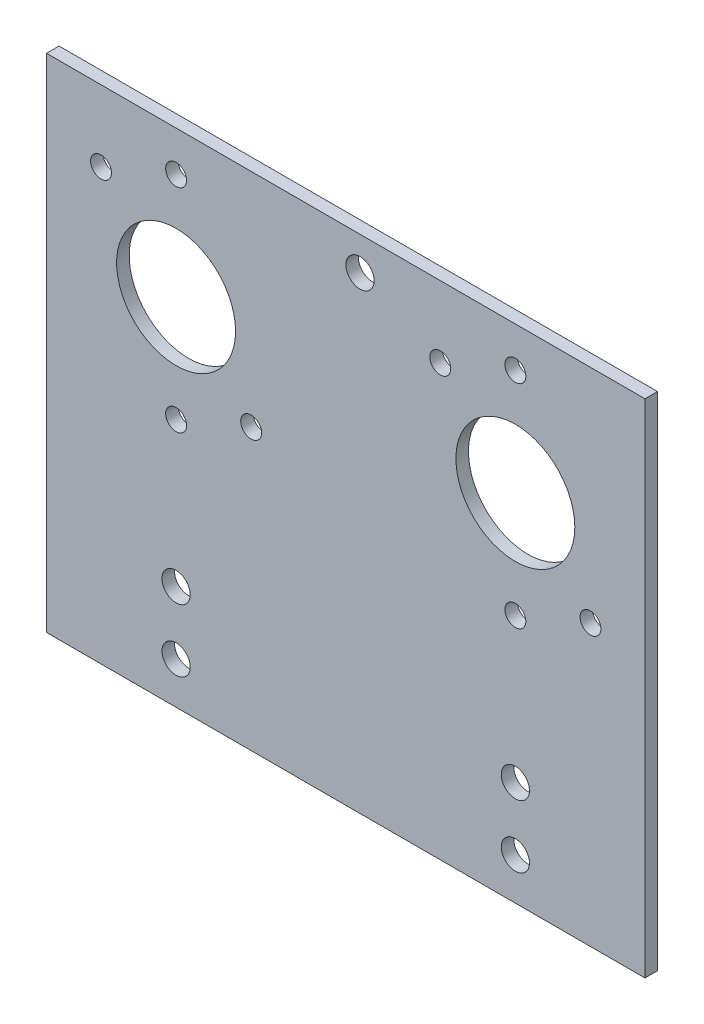
SolidWorks part; units mm, degrees
ref_plane "Front Plane" through (0, 0, 0) normal (0, 0, 1) x (1, 0, 0)
ref_plane "Top Plane" through (0, 0, 0) normal (0, 1, 0) x (1, 0, 0)
ref_plane "Right Plane" through (0, 0, 0) normal (1, 0, 0) x (0, 0, -1)
sketch "Sketch1" plane through (0, 0, 0) normal (0, 0, 1) x (1, 0, 0)
  line L1 (0, 0) -> (143.16, 0)
  line L2 (0, 0) -> (0, -120)
  line L3 (0, -120) -> (143.16, -120)
  line L4 (143.16, 0) -> (143.16, -120)
  dimension "D1" = 120
  dimension "D2" = 143.16
extrude "Boss-Extrude1" add sketch "Sketch1" along normal blind 3
sketch "Sketch2" plane through (0, 0, 3) normal (0, 0, 1) x (1, 0, 0)
  line L0 (0, 0) -> (0, -120) construction
  line L1 (143.16, -120) -> (143.16, 0) construction
  line L2 (0, -120) -> (143.16, -120) construction
  line L3 (143.16, 0) -> (0, 0) construction
  circle A0 centre (31, -35) radius 14.225
  circle A1 centre (112.16, -35) radius 14.225
  circle A2 centre (31, -110) radius 3.375
  circle A5 centre (112.16, -110) radius 3.375
  circle A7 centre (75, -8) radius 3.375
  circle A8 centre (31, -95) radius 3.375
  circle A9 centre (112.16, -95) radius 3.375
  dimension "D1" = 28.45
  dimension "D2" = 28.45
  dimension "D3" = 6.75
  dimension "D4" = 35
  dimension "D5" = 6.75
  dimension "D7" = 15
  dimension "D8" = 6.75
  dimension "D9" = 31
  dimension "D10" = 31
  dimension "D11" = 75
  dimension "D13" = 15
  dimension "D14" = 10
  dimension "D16" = 8
extrude "Cut-Extrude1" cut sketch "Sketch2" against normal through all
sketch "Sketch3" plane through (0, 0, 0) normal (0, 0, -1) x (-1, 0, 0)
  circle A0 centre (-48.9605, -52.9605) radius 2.0193 construction
  circle A1 centre (-31, -9.6) radius 2.0193 construction
  circle A2 centre (-13.0395, -17.0395) radius 2.0193 construction
  circle A3 centre (-48.9605, -52.9605) radius 2.0193
  circle A4 centre (-31, -9.6) radius 2.0193
  circle A5 centre (-13.0395, -17.0395) radius 2.0193
  circle A6 centre (-31, -60.4) radius 2.0193 construction
  circle A7 centre (-31, -60.4) radius 2.0193
  circle A8 centre (-94.1995, -17.0395) radius 2.0193 construction
  circle A9 centre (-112.16, -9.6) radius 2.0193 construction
  circle A10 centre (-94.1995, -17.0395) radius 2.0193
  circle A11 centre (-112.16, -9.6) radius 2.0193
  circle A12 centre (-112.16, -60.4) radius 2.0193 construction
  circle A13 centre (-130.1205, -52.9605) radius 2.0193 construction
  circle A14 centre (-112.16, -60.4) radius 2.0193
  circle A15 centre (-130.1205, -52.9605) radius 2.0193
  point P25 (-31, -60.4)
  point P26 (-48.9605, -52.9605)
  point P27 (-31, -9.6)
  point P28 (-13.0395, -17.0395)
  point P29 (-112.16, -60.4)
  point P30 (-130.1205, -52.9605)
  point P31 (-112.16, -9.6)
  point P32 (-94.1995, -17.0395)
extrude "Cut-Extrude2" cut sketch "Sketch3" against normal through all
sketch "Sketch6" plane through (0, 0, 3) normal (0, 0, 1) x (1, 0, 0)
  circle A0 centre (31, -60.4) radius 2.5
  circle A1 centre (48.9605, -52.9605) radius 2.5
  circle A3 centre (31, -9.6) radius 2.5
  circle A4 centre (13.0395, -17.0395) radius 2.5
  circle A5 centre (130.1205, -52.9605) radius 2.5
  circle A6 centre (112.16, -60.4) radius 2.5
  circle A7 centre (94.1995, -17.0395) radius 2.5
  circle A8 centre (112.16, -9.6) radius 2.5
  dimension "D1" = 5
  dimension "D2" = 5
  dimension "D3" = 5
  dimension "D4" = 5
  dimension "D5" = 5
  dimension "D6" = 5
  dimension "D7" = 5
  dimension "D8" = 5
extrude "Cut-Extrude3" cut sketch "Sketch6" against normal through all
